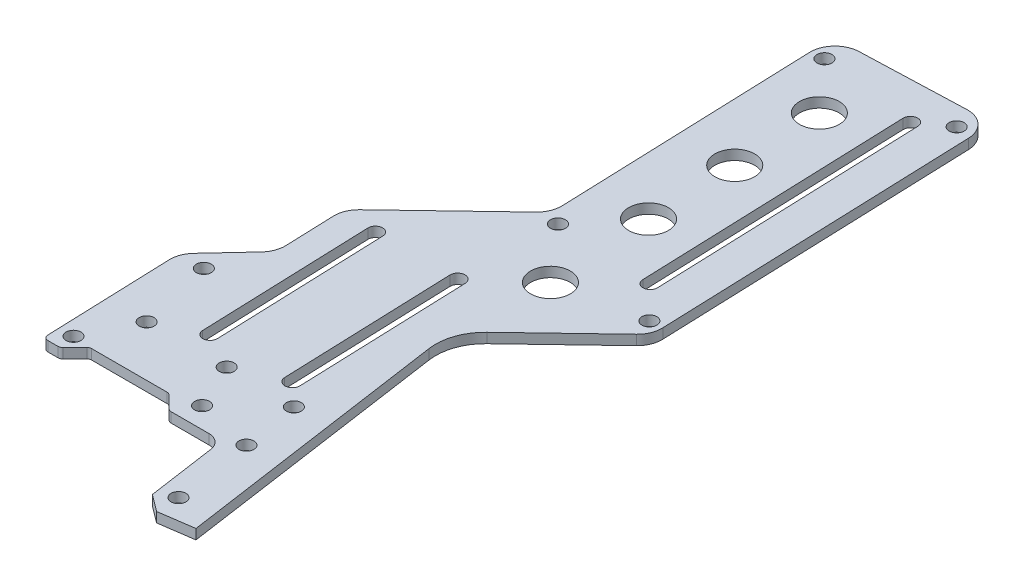
SolidWorks part; units mm, degrees
ref_plane "前视基准面" through (0, 0, 0) normal (0, 0, 1) x (1, 0, 0)
ref_plane "上视基准面" through (0, 0, 0) normal (0, 1, 0) x (1, 0, 0)
ref_plane "右视基准面" through (0, 0, 0) normal (1, 0, 0) x (0, 0, -1)
sketch "Sketch1" plane through (0, 0, 0) normal (0, 1, 0) x (1, 0, 0)
  line L6 (35.9461, 32.5892) -> (55.0686, 50.8364)
  line L7 (56.6136, 54.6329) -> (54.3224, 118.5515)
  line L8 (49.1465, 123.3692) -> (28.1497, 122.6166)
  line L9 (-4.0536, -9.5444) -> (-0.7001, -9.5444)
  line L10 (-0.7001, -9.5444) -> (2.2999, -6.5444)
  line L11 (18.2999, -6.5444) -> (2.2999, -6.5444)
  line L12 (26.2999, -9.5444) -> (21.2999, -9.5444)
  line L13 (18.2999, -6.5444) -> (21.2999, -9.5444)
  line L14 (23.3321, 117.4407) -> (25.1817, 65.8404)
  line L15 (23.6367, 62.044) -> (5.4762, 44.7149)
  line L16 (3.9312, 40.9184) -> (4.2853, 31.0397)
  line L17 (2.9485, 27.454) -> (-3.6599, 20.3542)
  line L18 (-4.9968, 16.7685) -> (-4.0536, -9.5444)
  line L19 (26.2999, -9.5444) -> (28.2999, -9.5444)
  line L20 (28.2999, -9.5444) -> (29.3174, -9.5444)
  line L21 (32.2867, -12.1163) -> (34.2711, -25.8807)
  line L22 (40.206, 3.0407) -> (35.9461, 32.5892)
  line L23 (40.206, 3.0407) -> (44.5979, -27.4229)
  line L24 (44.5979, -27.4229) -> (37.6684, -28.4219)
  line L26 (34.2711, -25.8807) -> (37.6684, -28.4219)
  arc A2 (55.0686, 50.8364) -> (56.6136, 54.6329) centre (51.6168, 54.4537) ccw
  arc A3 (-3.6599, 20.3542) -> (-4.9968, 16.7685) centre (0, 16.9476) ccw
  circle A4 centre (23.7704, -5.3703) radius 1.5
  circle A5 centre (19.5405, 3.8264) radius 1.5
  circle A6 centre (-1.2805, -6.2266) radius 1.5
  circle A7 centre (3.5641, 3.664) radius 1.5
  arc A8 (4.2853, 31.0397) -> (2.9485, 27.454) centre (-0.7115, 30.8606) cw
  arc A9 (5.4762, 44.7149) -> (3.9312, 40.9184) centre (8.928, 41.0975) ccw
  arc A10 (25.1817, 65.8404) -> (23.6367, 62.044) centre (20.1849, 65.6613) cw
  arc A11 (54.3224, 118.5515) -> (49.1465, 123.3692) centre (49.3257, 118.3724) ccw
  arc A12 (28.1497, 122.6166) -> (23.3321, 117.4407) centre (28.3289, 117.6198) ccw
  arc A13 (29.3174, -9.5444) -> (32.2867, -12.1163) centre (29.3174, -12.5444) cw
  dimension "D3" = 3
  dimension "D2" = 135
extrude "Boss-Extrude1" add sketch "Sketch1" along normal blind 2
sketch "Sketch2" plane through (0, 0, 0) normal (0, -1, 0) x (1, 0, 0)
  line L16 (10.9319, -42.3885) -> (12.1697, -7.8569) construction
  line L19 (9.4767, -42.3363) -> (10.7145, -7.8047)
  line L22 (12.3872, -42.4407) -> (13.625, -7.9091)
  line L25 (27.4452, -42.4518) -> (28.683, -7.9202) construction
  line L26 (25.9469, -42.3981) -> (27.1847, -7.8665)
  line L27 (28.9435, -42.5055) -> (30.1813, -7.9739)
  line L32 (45.6918, -115.4691) -> (47.6415, -61.0787) construction
  line L33 (44.2395, -115.4171) -> (46.1892, -61.0266)
  line L34 (47.1441, -115.5212) -> (49.0938, -61.1307)
  arc A16 (9.4767, -42.3363) -> (12.3872, -42.4407) centre (10.9319, -42.3885) ccw
  arc A17 (13.625, -7.9091) -> (10.7145, -7.8047) centre (12.1697, -7.8569) ccw
  arc A18 (25.9469, -42.3981) -> (28.9435, -42.5055) centre (27.4452, -42.4518) ccw
  arc A19 (30.1813, -7.9739) -> (27.1847, -7.8665) centre (28.683, -7.9202) ccw
  arc A24 (44.2395, -115.4171) -> (47.1441, -115.5212) centre (45.6918, -115.4691) ccw
  arc A25 (49.0938, -61.1307) -> (46.1892, -61.0266) centre (47.6415, -61.0787) ccw
  circle A34 centre (34.8935, -107.9094) radius 4
  circle A35 centre (35.5006, -90.2447) radius 4
  circle A36 centre (37.3756, -51.2344) radius 4
  circle A37 centre (36.1937, -72.1788) radius 4
  point P19 (46.6667, -88.2739)
  point P38 (11.5508, -25.1227)
  point P45 (28.0641, -25.186)
  point P75 (30.6759, -3.7668)
extrude "Cut-Extrude1" cut sketch "Sketch2" against normal through all
sketch "Sketch3" plane through (0, 2, 0) normal (0, 1, 0) x (1, 0, 0)
  line L0 (25.9434, 117.8711) -> (27.9394, 62.1871) construction
  circle A0 centre (0, 18.7605) radius 1.5
  circle A1 centre (54.0546, 54.4882) radius 1.5
  circle A2 centre (25.9434, 117.8711) radius 1.5
  circle A3 centre (51.146, 119.3117) radius 1.5
  circle A4 centre (27.9394, 62.1871) radius 1.5
  circle A5 centre (33.2404, 3.6609) radius 1.5
extrude "Cut-Extrude2" cut sketch "Sketch3" against normal blind 10
fillet "Fillet1" radius 10 1 edges at (35.9461, 1, -32.5892)
sketch "Sketch4" plane through (0, 0, 0) normal (0, -1, 0) x (1, 0, 0)
  arc A4 (36.8062, 22.4407) -> (37.2151, 25.2772) centre (37.4497, 23.7957) ccw
  arc A5 (37.2151, 25.2772) -> (36.8062, 22.4407) centre (37.4497, 23.7957) ccw
  arc A6 (34.9091, 9.282) -> (34.5002, 6.4455) centre (35.1437, 7.8004) ccw
  arc A7 (34.5002, 6.4455) -> (34.9091, 9.282) centre (35.1437, 7.8004) ccw
extrude "Cut-Extrude3" cut sketch "Sketch4" against normal blind 23
fillet "Fillet2" radius 1 5 edges at (21.2999, 1, 9.5444) (18.2999, 1, 6.5444) (2.2999, 1, 6.5444) (-0.7001, 1, 9.5444) (-4.0536, 1, 9.5444)
